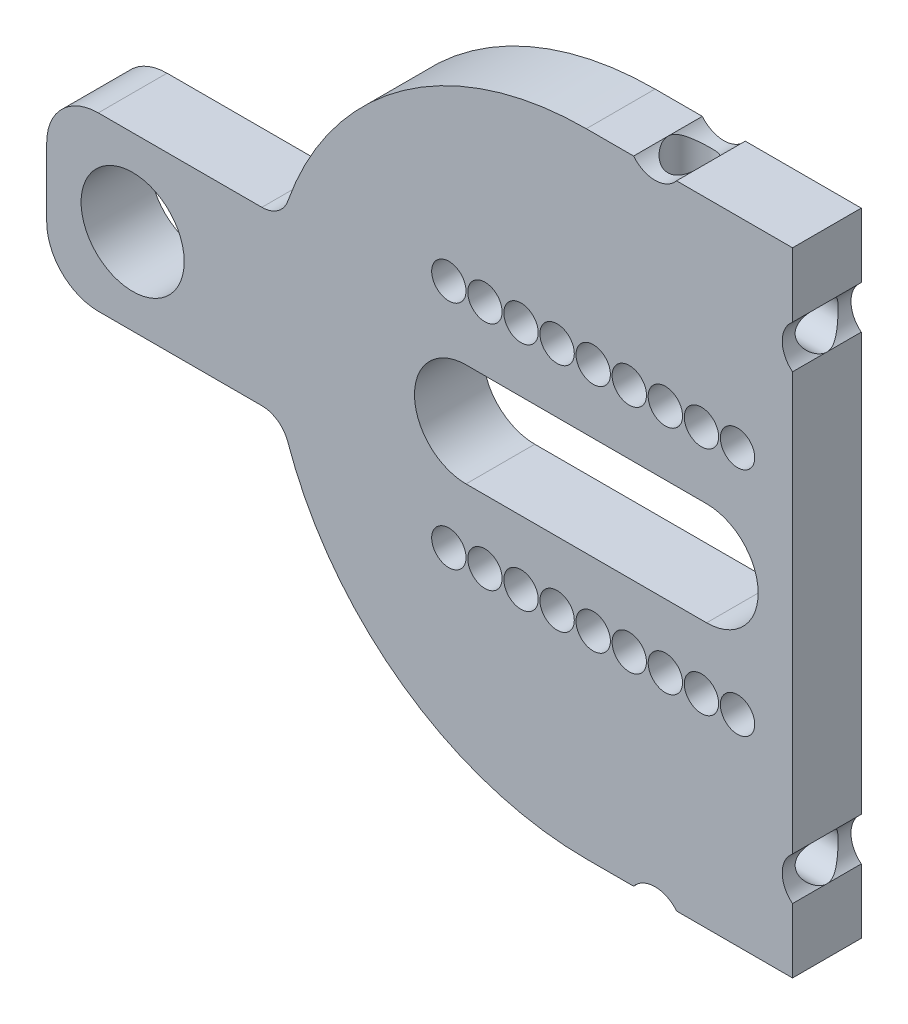
SolidWorks part; units mm, degrees
material "Aleación 1060"
ref_plane "Alzado" through (0, 0, 0) normal (0, 0, 1) x (1, 0, 0)
ref_plane "Planta" through (0, 0, 0) normal (0, 1, 0) x (1, 0, 0)
ref_plane "Vista lateral" through (0, 0, 0) normal (1, 0, 0) x (0, 0, -1)
sketch "Croquis1" plane through (0, 0, 0) normal (0, 0, 1) x (1, 0, 0)
  line L0 (-3, 0) -> (3, 0) construction
  line L1 (3, 0) -> (3, 7) construction
  line L2 (3, 0) -> (3, -7) construction
  line L3 (0, 0) -> (6.72, 0) construction
  line L4 (5.37, 0) -> (5.37, 8) construction
  line L5 (5.37, 0) -> (5.37, -8) construction
  line L6 (8.07, 8) -> (8.07, -8) construction
  line L7 (0, 0) -> (0, 18.4) construction
  line L8 (-8.07, 8) -> (-8.07, -8) construction
  line L9 (-5.37, 0) -> (-5.37, -8) construction
  line L10 (-5.37, 0) -> (-5.37, 8) construction
  line L11 (-3, 0) -> (-3, -7) construction
  line L12 (-3, 0) -> (-3, 7) construction
  line L13 (0, -18.4) -> (-11, -18.4) construction
  line L14 (-11, -14.7499) -> (-11, -24.7499) construction
  line L15 (11, -14.7499) -> (11, -24.7499) construction
  line L16 (-11, -24.7499) -> (11, -24.7499) construction
  line L17 (7, 3) -> (-7, 3)
  line L18 (12, 0) -> (12, 18.4)
  line L19 (12, 18.4) -> (0, 18.4)
  line L20 (12, 0) -> (12, -18.4)
  line L21 (12, -18.4) -> (0, -18.4)
  line L22 (8, 5.37) -> (-8, 5.37) construction
  line L23 (8, 8.07) -> (-8, 8.07) construction
  line L24 (8, -8.07) -> (-8, -8.07) construction
  line L25 (8, -5.37) -> (-8, -5.37) construction
  line L26 (7, -3) -> (-7, -3)
  line L27 (-8, -6.72) -> (-5.9, -6.72) construction
  arc A0 (11, -14.7499) -> (-11, -14.7499) centre (0, 0) ccw construction
  arc A1 (5.37, 8) -> (8.07, 8) centre (6.72, 8) cw construction
  arc A2 (5.37, -8) -> (8.07, -8) centre (6.72, -8) ccw construction
  arc A3 (-5.37, -8) -> (-8.07, -8) centre (-6.72, -8) cw construction
  arc A4 (-5.37, 8) -> (-8.07, 8) centre (-6.72, 8) ccw construction
  arc A5 (-3, 7) -> (3, 7) centre (0, 7) cw construction
  arc A6 (-3, -7) -> (3, -7) centre (0, -7) ccw construction
  arc A7 (0, 18.4) -> (0, -18.4) centre (0, 0) ccw
  arc A8 (-8, 5.37) -> (-8, 8.07) centre (-8, 6.72) cw construction
  arc A9 (-8, -5.37) -> (-8, -8.07) centre (-8, -6.72) ccw construction
  arc A10 (-7, -3) -> (-7, 3) centre (-7, 0) cw
  arc A11 (8, -5.37) -> (8, -8.07) centre (8, -6.72) cw construction
  arc A12 (7, -3) -> (7, 3) centre (7, 0) ccw
  arc A13 (8, 5.37) -> (8, 8.07) centre (8, 6.72) ccw construction
  circle A14 centre (-8, -6.72) radius 1
  circle A15 centre (-8, 6.72) radius 1
  circle A16 centre (-5.9, -6.72) radius 1
  circle A17 centre (-5.9, 6.72) radius 1
  circle A18 centre (-3.8, -6.72) radius 1
  circle A19 centre (-3.8, 6.72) radius 1
  circle A20 centre (-1.7, -6.72) radius 1
  circle A21 centre (-1.7, 6.72) radius 1
  circle A22 centre (0.4, -6.72) radius 1
  circle A23 centre (0.4, 6.72) radius 1
  circle A24 centre (2.5, -6.72) radius 1
  circle A25 centre (2.5, 6.72) radius 1
  circle A26 centre (4.6, -6.72) radius 1
  circle A27 centre (4.6, 6.72) radius 1
  circle A28 centre (6.7, -6.72) radius 1
  circle A29 centre (6.7, 6.72) radius 1
  circle A30 centre (8.8, -6.72) radius 1
  circle A31 centre (8.8, 6.72) radius 1
  point P1 (0, 5.37)
  point P37 (0, 8.07)
  point P45 (0, -5.37)
  point P46 (0, -3)
  point P47 (0, 3)
  point P59 (0, -8.07)
  dimension "D1" = 36.8
  dimension "D17" = 2
  dimension "D18" = 2
  dimension "D2" = 7
  dimension "D3" = 7
  dimension "D4" = 2.7
  dimension "D5" = 11
  dimension "D6" = 10
  dimension "D7" = 3
  dimension "D8" = 6.72
  dimension "D9" = 8
  dimension "D10" = 8
  dimension "D11" = 12
  dimension "D12" = 7
  dimension "D13" = 3
  dimension "D14" = 8
  dimension "D15" = 2.7
  dimension "D16" = 6.72
  dimension "D20" = 2.1
  dimension "D19" = 9
extrude "Saliente-Extruir1" add sketch "Croquis1" along normal blind 4
sketch "Croquis5" plane through (12, 0, 0) normal (1, 0, 0) x (0, 0, -1)
  line L0 (-4, 18.4) -> (0, 18.4) construction
  line L1 (0, 0) -> (-4, 0) construction
  line L2 (0, -18.4) -> (0, 18.4) construction
  line L3 (-4, -18.4) -> (-4, 18.4) construction
  circle A0 centre (-2, 13.4) radius 1.25
  circle A1 centre (-2, -13.4) radius 1.25
  point P5 (-2, 18.4)
  dimension "D1" = 2.5
  dimension "D2" = 5
extrude "Cortar-Extruir2" cut sketch "Croquis5" against normal blind 6
sketch "Croquis6" plane through (0, 0, 4) normal (0, 0, 1) x (1, 0, 0)
  line L0 (-18.4, 0) -> (-31.4, 0) construction
  line L1 (-31.4, 5) -> (-31.4, -5)
  line L2 (-31.4, -5) -> (-17.7076, -5)
  line L3 (-31.4, 5) -> (-17.7076, 5)
  line L4 (-29.4, 0) -> (-31.4, 0) construction
  arc A0 (0, 18.4) -> (0, -18.4) centre (0, 0) ccw construction
  arc A1 (-17.7076, -5) -> (-17.7076, 5) centre (0, 0) cw
  circle A2 centre (-26.4, 0) radius 3
  dimension "D3" = 2
  dimension "D1" = 13
  dimension "D2" = 5
extrude "Saliente-Extruir2" add sketch "Croquis6" against normal up to vertex (4 mm away) up to point (0, -18.4, 0)
sketch "Croquis8" plane through (0, 18.4, 0) normal (0, 1, 0) x (1, 0, 0)
  line L0 (12, -4) -> (12, 0) construction
  circle A0 centre (4, -2) radius 1.25
  dimension "D1" = 8
  dimension "D2" = 2.5
extrude "Cortar-Extruir4" cut sketch "Croquis8" against normal blind 5
extrude "Cortar-Extruir5" cut sketch "Croquis8<2>" along normal blind 5 from surface starting at face at (6, -18.4, 2)
sketch "Croquis8<2>" plane through (0, 18.4, 0) normal (0, 1, 0) x (1, 0, 0) same geometry as "Croquis8"
fillet "Redondeo1" radius 3 2 edges at (-31.4, -5, 2) (-31.4, 5, 2)
fillet "Redondeo2" radius 1.6 2 edges at (-17.7076, 5, 2) (-17.7076, -5, 2)
sketch "Croquis7" plane through (0, 0, 4) normal (0, 0, 1) x (1, 0, 0)
  line L0 (12, -18.4) -> (12, 18.4) construction
  line L1 (12, 18.4) -> (0, 18.4) construction
  line L2 (12, 0) -> (-10, 0) construction
  circle A0 centre (4, 19.4) radius 1.6
  arc A1 (-7, 3) -> (-7, -3) centre (-7, 0) ccw construction
  circle A2 centre (4, -19.4) radius 1.6
  circle A3 centre (13, 13.4) radius 1.6
  circle A4 centre (13, -13.4) radius 1.6
  dimension "D1" = 8
  dimension "D2" = 3.2
  dimension "D4" = 3.2
  dimension "D3" = 1
  dimension "D5" = 1
  dimension "D6" = 5
extrude "Cortar-Extruir3" cut sketch "Croquis7" against normal up to vertex (4 mm away) up to point (12, 18.4, 0)
